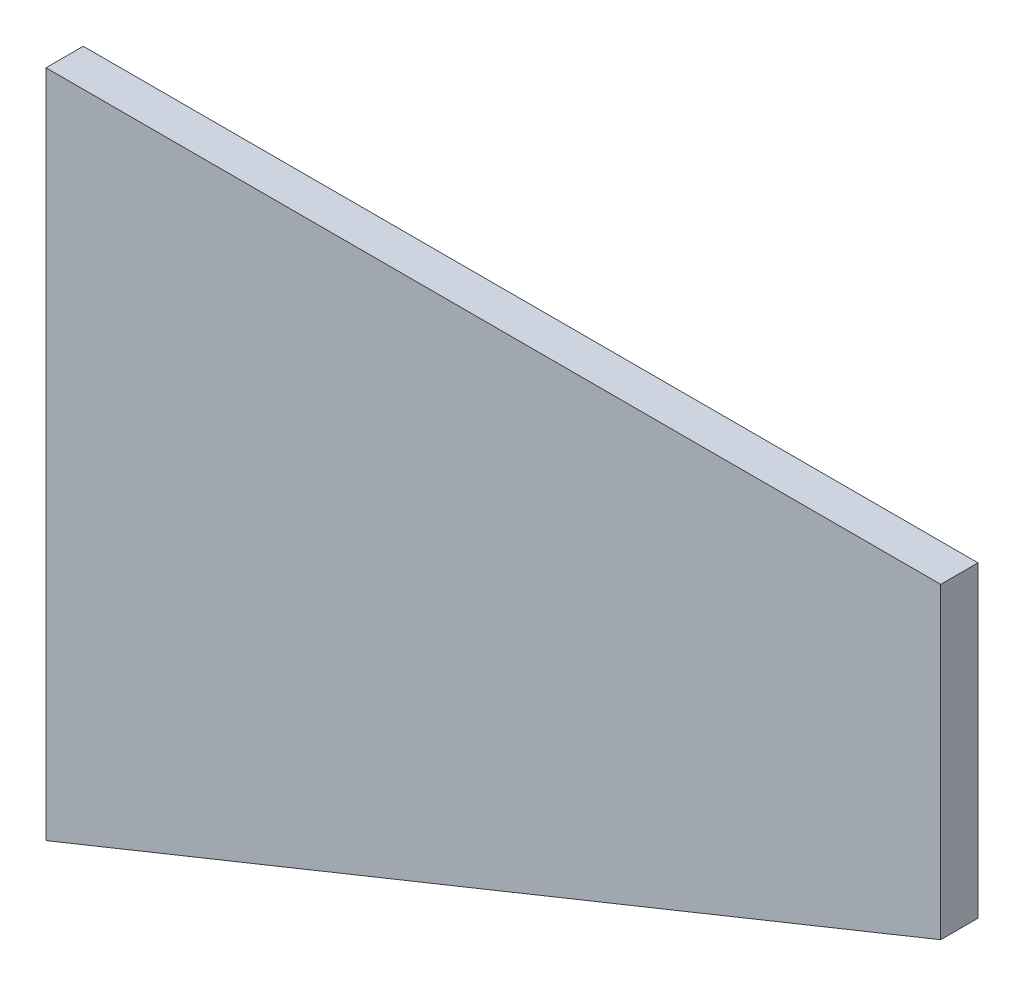
SolidWorks part; units mm, degrees
material "Beech"
ref_plane "Front Plane" through (0, 0, 0) normal (0, 0, 1) x (1, 0, 0)
ref_plane "Top Plane" through (0, 0, 0) normal (0, 1, 0) x (1, 0, 0)
ref_plane "Right Plane" through (0, 0, 0) normal (1, 0, 0) x (0, 0, -1)
sketch "Sketch1" plane through (0, 0, 0) normal (0, 0, 1) x (1, 0, 0)
  line L0 (2683.51, 6641.7419) -> (3140.71, 6826.4627) construction
  line L1 (2683.51, 7002.78) -> (2683.51, 5935.98) construction
  line L8 (2683.51, 6983.73) -> (2683.51, 6641.7419)
  line L9 (2683.51, 6641.7419) -> (3140.71, 6826.4627)
  line L10 (3140.71, 6826.4627) -> (3140.71, 6983.73)
  line L11 (3140.71, 6983.73) -> (2683.51, 6983.73)
extrude "Boss-Extrude1" add sketch "Sketch1" along normal blind 19.05
